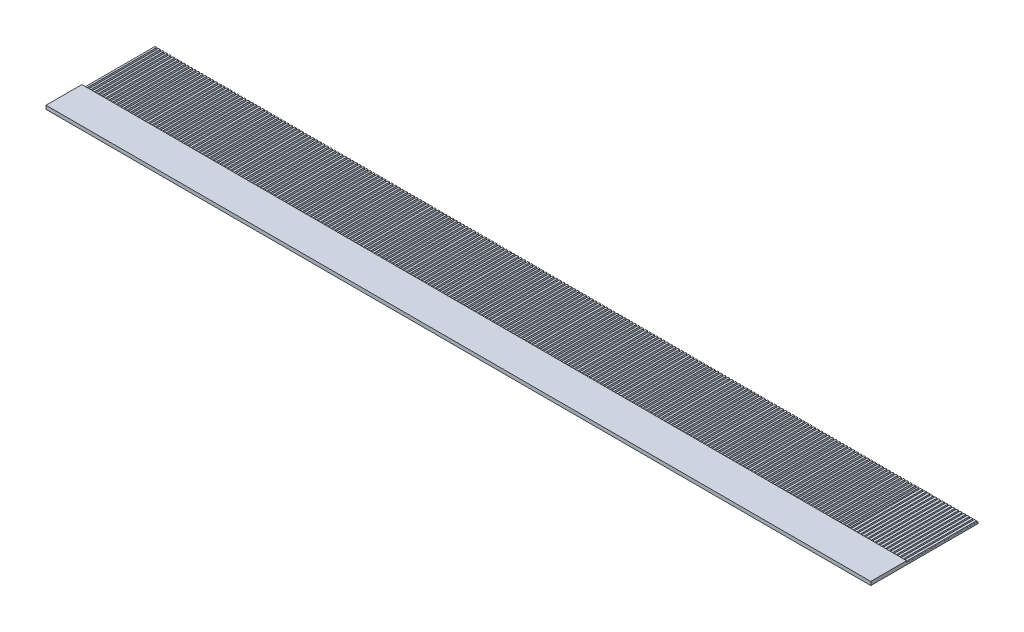
SolidWorks part; units mm, degrees
ref_plane "Front Plane" through (0, 0, 0) normal (0, 0, 1) x (1, 0, 0)
ref_plane "Top Plane" through (0, 0, 0) normal (0, 1, 0) x (1, 0, 0)
ref_plane "Right Plane" through (0, 0, 0) normal (1, 0, 0) x (0, 0, -1)
sketch "Sketch1" plane through (0, 0, 0) normal (0, 1, 0) x (1, 0, 0)
  line L1 (0, 0) -> (115, 0)
  line L2 (0, 0) -> (0, 15)
  line L3 (0, 15) -> (115, 15)
  line L4 (115, 0) -> (115, 15)
extrude "Boss-Extrude1" add sketch "Sketch1" along normal blind 0.5
sketch "Sketch3" plane through (0, 0.5, 0) normal (0, 1, 0) x (1, 0, 0)
  line L0 (115, 0) -> (115, 15) construction
  line L1 (0, 15) -> (115, 15)
  line L2 (0, 15) -> (0, 5)
  line L3 (0, 5) -> (115, 5)
  line L4 (115, 15) -> (115, 5)
extrude "Cut-Extrude3" cut sketch "Sketch3" against normal blind 0.25
sketch "Sketch5" plane through (0, 0.25, 0) normal (0, 1, 0) x (1, 0, 0)
  line L0 (0, 5) -> (115, 5) construction
  line L1 (0, 15) -> (0.25, 15)
  line L2 (0, 15) -> (0, 5)
  line L3 (0, 5) -> (0.25, 5)
  line L4 (0.25, 15) -> (0.25, 5)
  line L5 (0.4954, 14.999) -> (0.7454, 14.999)
  line L6 (0.4954, 14.999) -> (0.4954, 4.999)
  line L7 (0.4954, 4.999) -> (0.7454, 4.999)
  line L8 (0.7454, 14.999) -> (0.7454, 4.999)
  line L9 (0.9914, 15.0028) -> (1.2414, 15.0028)
  line L10 (0.9914, 15.0028) -> (0.9914, 5.0028)
  line L11 (0.9914, 5.0028) -> (1.2414, 5.0028)
  line L12 (1.2414, 15.0028) -> (1.2414, 5.0028)
  line L13 (1.4959, 15.002) -> (1.7459, 15.002)
  line L14 (1.4959, 15.002) -> (1.4959, 5.002)
  line L15 (1.4959, 5.002) -> (1.7459, 5.002)
  line L16 (1.7459, 15.002) -> (1.7459, 5.002)
  line L17 (1.9913, 15.0009) -> (2.2413, 15.0009)
  line L18 (1.9913, 15.0009) -> (1.9913, 5.0009)
  line L19 (1.9913, 5.0009) -> (2.2413, 5.0009)
  line L20 (2.2413, 15.0009) -> (2.2413, 5.0009)
  line L21 (2.4872, 15.0047) -> (2.7372, 15.0047)
  line L22 (2.4872, 15.0047) -> (2.4872, 5.0047)
  line L23 (2.4872, 5.0047) -> (2.7372, 5.0047)
  line L24 (2.7372, 15.0047) -> (2.7372, 5.0047)
  line L25 (3.0149, 14.998) -> (3.2649, 14.998)
  line L26 (3.0149, 14.998) -> (3.0149, 4.998)
  line L27 (3.0149, 4.998) -> (3.2649, 4.998)
  line L28 (3.2649, 14.998) -> (3.2649, 4.998)
  line L29 (3.5104, 14.9969) -> (3.7604, 14.9969)
  line L30 (3.5104, 14.9969) -> (3.5104, 4.9969)
  line L31 (3.5104, 4.9969) -> (3.7604, 4.9969)
  line L32 (3.7604, 14.9969) -> (3.7604, 4.9969)
  line L33 (4.0063, 15.0007) -> (4.2563, 15.0007)
  line L34 (4.0063, 15.0007) -> (4.0063, 5.0007)
  line L35 (4.0063, 5.0007) -> (4.2563, 5.0007)
  line L36 (4.2563, 15.0007) -> (4.2563, 5.0007)
  line L37 (4.5108, 14.9999) -> (4.7608, 14.9999)
  line L38 (4.5108, 14.9999) -> (4.5108, 4.9999)
  line L39 (4.5108, 4.9999) -> (4.7608, 4.9999)
  line L40 (4.7608, 14.9999) -> (4.7608, 4.9999)
  line L41 (5.0062, 14.9989) -> (5.2562, 14.9989)
  line L42 (5.0062, 14.9989) -> (5.0062, 4.9989)
  line L43 (5.0062, 4.9989) -> (5.2562, 4.9989)
  line L44 (5.2562, 14.9989) -> (5.2562, 4.9989)
  line L45 (5.5021, 15.0027) -> (5.7521, 15.0027)
  line L46 (5.5021, 15.0027) -> (5.5021, 5.0027)
  line L47 (5.5021, 5.0027) -> (5.7521, 5.0027)
  line L48 (5.7521, 15.0027) -> (5.7521, 5.0027)
  line L49 (5.9811, 14.9963) -> (6.2311, 14.9963)
  line L50 (5.9811, 14.9963) -> (5.9811, 4.9963)
  line L51 (5.9811, 4.9963) -> (6.2311, 4.9963)
  line L52 (6.2311, 14.9963) -> (6.2311, 4.9963)
  line L53 (6.4766, 14.9953) -> (6.7266, 14.9953)
  line L54 (6.4766, 14.9953) -> (6.4766, 4.9953)
  line L55 (6.4766, 4.9953) -> (6.7266, 4.9953)
  line L56 (6.7266, 14.9953) -> (6.7266, 4.9953)
  line L57 (6.9725, 14.9991) -> (7.2225, 14.9991)
  line L58 (6.9725, 14.9991) -> (6.9725, 4.9991)
  line L59 (6.9725, 4.9991) -> (7.2225, 4.9991)
  line L60 (7.2225, 14.9991) -> (7.2225, 4.9991)
  line L61 (7.477, 14.9983) -> (7.727, 14.9983)
  line L62 (7.477, 14.9983) -> (7.477, 4.9983)
  line L63 (7.477, 4.9983) -> (7.727, 4.9983)
  line L64 (7.727, 14.9983) -> (7.727, 4.9983)
  line L65 (7.9724, 14.9973) -> (8.2224, 14.9973)
  line L66 (7.9724, 14.9973) -> (7.9724, 4.9973)
  line L67 (7.9724, 4.9973) -> (8.2224, 4.9973)
  line L68 (8.2224, 14.9973) -> (8.2224, 4.9973)
  line L69 (8.4683, 15.0011) -> (8.7183, 15.0011)
  line L70 (8.4683, 15.0011) -> (8.4683, 5.0011)
  line L71 (8.4683, 5.0011) -> (8.7183, 5.0011)
  line L72 (8.7183, 15.0011) -> (8.7183, 5.0011)
  line L73 (8.996, 14.9943) -> (9.246, 14.9943)
  line L74 (8.996, 14.9943) -> (8.996, 4.9943)
  line L75 (8.996, 4.9943) -> (9.246, 4.9943)
  line L76 (9.246, 14.9943) -> (9.246, 4.9943)
  line L77 (9.4915, 14.9933) -> (9.7415, 14.9933)
  line L78 (9.4915, 14.9933) -> (9.4915, 4.9933)
  line L79 (9.4915, 4.9933) -> (9.7415, 4.9933)
  line L80 (9.7415, 14.9933) -> (9.7415, 4.9933)
  line L81 (9.9874, 14.9971) -> (10.2374, 14.9971)
  line L82 (9.9874, 14.9971) -> (9.9874, 4.9971)
  line L83 (9.9874, 4.9971) -> (10.2374, 4.9971)
  line L84 (10.2374, 14.9971) -> (10.2374, 4.9971)
  line L85 (10.4919, 14.9963) -> (10.7419, 14.9963)
  line L86 (10.4919, 14.9963) -> (10.4919, 4.9963)
  line L87 (10.4919, 4.9963) -> (10.7419, 4.9963)
  line L88 (10.7419, 14.9963) -> (10.7419, 4.9963)
  line L89 (10.9873, 14.9952) -> (11.2373, 14.9952)
  line L90 (10.9873, 14.9952) -> (10.9873, 4.9952)
  line L91 (10.9873, 4.9952) -> (11.2373, 4.9952)
  line L92 (11.2373, 14.9952) -> (11.2373, 4.9952)
  line L93 (11.4833, 14.999) -> (11.7333, 14.999)
  line L94 (11.4833, 14.999) -> (11.4833, 4.999)
  line L95 (11.4833, 4.999) -> (11.7333, 4.999)
  line L96 (11.7333, 14.999) -> (11.7333, 4.999)
  line L97 (11.9724, 15.0297) -> (12.2224, 15.0297)
  line L98 (11.9724, 15.0297) -> (11.9724, 5.0297)
  line L99 (11.9724, 5.0297) -> (12.2224, 5.0297)
  line L100 (12.2224, 15.0297) -> (12.2224, 5.0297)
  line L101 (12.4678, 15.0286) -> (12.7178, 15.0286)
  line L102 (12.4678, 15.0286) -> (12.4678, 5.0286)
  line L103 (12.4678, 5.0286) -> (12.7178, 5.0286)
  line L104 (12.7178, 15.0286) -> (12.7178, 5.0286)
  line L105 (12.9637, 15.0325) -> (13.2137, 15.0325)
  line L106 (12.9637, 15.0325) -> (12.9637, 5.0325)
  line L107 (12.9637, 5.0325) -> (13.2137, 5.0325)
  line L108 (13.2137, 15.0325) -> (13.2137, 5.0325)
  line L109 (13.4683, 15.0316) -> (13.7183, 15.0316)
  line L110 (13.4683, 15.0316) -> (13.4683, 5.0316)
  line L111 (13.4683, 5.0316) -> (13.7183, 5.0316)
  line L112 (13.7183, 15.0316) -> (13.7183, 5.0316)
  line L113 (13.9637, 15.0306) -> (14.2137, 15.0306)
  line L114 (13.9637, 15.0306) -> (13.9637, 5.0306)
  line L115 (13.9637, 5.0306) -> (14.2137, 5.0306)
  line L116 (14.2137, 15.0306) -> (14.2137, 5.0306)
  line L117 (14.4596, 15.0344) -> (14.7096, 15.0344)
  line L118 (14.4596, 15.0344) -> (14.4596, 5.0344)
  line L119 (14.4596, 5.0344) -> (14.7096, 5.0344)
  line L120 (14.7096, 15.0344) -> (14.7096, 5.0344)
  line L121 (14.9873, 15.0276) -> (15.2373, 15.0276)
  line L122 (14.9873, 15.0276) -> (14.9873, 5.0276)
  line L123 (14.9873, 5.0276) -> (15.2373, 5.0276)
  line L124 (15.2373, 15.0276) -> (15.2373, 5.0276)
  line L125 (15.4827, 15.0266) -> (15.7327, 15.0266)
  line L126 (15.4827, 15.0266) -> (15.4827, 5.0266)
  line L127 (15.4827, 5.0266) -> (15.7327, 5.0266)
  line L128 (15.7327, 15.0266) -> (15.7327, 5.0266)
  line L129 (15.9787, 15.0304) -> (16.2287, 15.0304)
  line L130 (15.9787, 15.0304) -> (15.9787, 5.0304)
  line L131 (15.9787, 5.0304) -> (16.2287, 5.0304)
  line L132 (16.2287, 15.0304) -> (16.2287, 5.0304)
  line L133 (16.4832, 15.0296) -> (16.7332, 15.0296)
  line L134 (16.4832, 15.0296) -> (16.4832, 5.0296)
  line L135 (16.4832, 5.0296) -> (16.7332, 5.0296)
  line L136 (16.7332, 15.0296) -> (16.7332, 5.0296)
  line L137 (16.9786, 15.0286) -> (17.2286, 15.0286)
  line L138 (16.9786, 15.0286) -> (16.9786, 5.0286)
  line L139 (16.9786, 5.0286) -> (17.2286, 5.0286)
  line L140 (17.2286, 15.0286) -> (17.2286, 5.0286)
  line L141 (17.4745, 15.0324) -> (17.7245, 15.0324)
  line L142 (17.4745, 15.0324) -> (17.4745, 5.0324)
  line L143 (17.4745, 5.0324) -> (17.7245, 5.0324)
  line L144 (17.7245, 15.0324) -> (17.7245, 5.0324)
  line L145 (17.9535, 15.026) -> (18.2035, 15.026)
  line L146 (17.9535, 15.026) -> (17.9535, 5.026)
  line L147 (17.9535, 5.026) -> (18.2035, 5.026)
  line L148 (18.2035, 15.026) -> (18.2035, 5.026)
  line L149 (18.449, 15.025) -> (18.699, 15.025)
  line L150 (18.449, 15.025) -> (18.449, 5.025)
  line L151 (18.449, 5.025) -> (18.699, 5.025)
  line L152 (18.699, 15.025) -> (18.699, 5.025)
  line L153 (18.9449, 15.0288) -> (19.1949, 15.0288)
  line L154 (18.9449, 15.0288) -> (18.9449, 5.0288)
  line L155 (18.9449, 5.0288) -> (19.1949, 5.0288)
  line L156 (19.1949, 15.0288) -> (19.1949, 5.0288)
  line L157 (19.4494, 15.028) -> (19.6994, 15.028)
  line L158 (19.4494, 15.028) -> (19.4494, 5.028)
  line L159 (19.4494, 5.028) -> (19.6994, 5.028)
  line L160 (19.6994, 15.028) -> (19.6994, 5.028)
  line L161 (19.9448, 15.0269) -> (20.1948, 15.0269)
  line L162 (19.9448, 15.0269) -> (19.9448, 5.0269)
  line L163 (19.9448, 5.0269) -> (20.1948, 5.0269)
  line L164 (20.1948, 15.0269) -> (20.1948, 5.0269)
  line L165 (20.4407, 15.0308) -> (20.6907, 15.0308)
  line L166 (20.4407, 15.0308) -> (20.4407, 5.0308)
  line L167 (20.4407, 5.0308) -> (20.6907, 5.0308)
  line L168 (20.6907, 15.0308) -> (20.6907, 5.0308)
  line L169 (20.9684, 15.024) -> (21.2184, 15.024)
  line L170 (20.9684, 15.024) -> (20.9684, 5.024)
  line L171 (20.9684, 5.024) -> (21.2184, 5.024)
  line L172 (21.2184, 15.024) -> (21.2184, 5.024)
  line L173 (21.4639, 15.0229) -> (21.7139, 15.0229)
  line L174 (21.4639, 15.0229) -> (21.4639, 5.0229)
  line L175 (21.4639, 5.0229) -> (21.7139, 5.0229)
  line L176 (21.7139, 15.0229) -> (21.7139, 5.0229)
  line L177 (21.9598, 15.0268) -> (22.2098, 15.0268)
  line L178 (21.9598, 15.0268) -> (21.9598, 5.0268)
  line L179 (21.9598, 5.0268) -> (22.2098, 5.0268)
  line L180 (22.2098, 15.0268) -> (22.2098, 5.0268)
  line L181 (22.4643, 15.0259) -> (22.7143, 15.0259)
  line L182 (22.4643, 15.0259) -> (22.4643, 5.0259)
  line L183 (22.4643, 5.0259) -> (22.7143, 5.0259)
  line L184 (22.7143, 15.0259) -> (22.7143, 5.0259)
  line L185 (22.9597, 15.0249) -> (23.2097, 15.0249)
  line L186 (22.9597, 15.0249) -> (22.9597, 5.0249)
  line L187 (22.9597, 5.0249) -> (23.2097, 5.0249)
  line L188 (23.2097, 15.0249) -> (23.2097, 5.0249)
  line L189 (23.4556, 15.0287) -> (23.7056, 15.0287)
  line L190 (23.4556, 15.0287) -> (23.4556, 5.0287)
  line L191 (23.4556, 5.0287) -> (23.7056, 5.0287)
  line L192 (23.7056, 15.0287) -> (23.7056, 5.0287)
  line L193 (23.9759, 15.0248) -> (24.2259, 15.0248)
  line L194 (23.9759, 15.0248) -> (23.9759, 5.0248)
  line L195 (23.9759, 5.0248) -> (24.2259, 5.0248)
  line L196 (24.2259, 15.0248) -> (24.2259, 5.0248)
  line L197 (24.4713, 15.0237) -> (24.7213, 15.0237)
  line L198 (24.4713, 15.0237) -> (24.4713, 5.0237)
  line L199 (24.4713, 5.0237) -> (24.7213, 5.0237)
  line L200 (24.7213, 15.0237) -> (24.7213, 5.0237)
  line L201 (24.9672, 15.0275) -> (25.2172, 15.0275)
  line L202 (24.9672, 15.0275) -> (24.9672, 5.0275)
  line L203 (24.9672, 5.0275) -> (25.2172, 5.0275)
  line L204 (25.2172, 15.0275) -> (25.2172, 5.0275)
  line L205 (25.4717, 15.0267) -> (25.7217, 15.0267)
  line L206 (25.4717, 15.0267) -> (25.4717, 5.0267)
  line L207 (25.4717, 5.0267) -> (25.7217, 5.0267)
  line L208 (25.7217, 15.0267) -> (25.7217, 5.0267)
  line L209 (25.9672, 15.0257) -> (26.2172, 15.0257)
  line L210 (25.9672, 15.0257) -> (25.9672, 5.0257)
  line L211 (25.9672, 5.0257) -> (26.2172, 5.0257)
  line L212 (26.2172, 15.0257) -> (26.2172, 5.0257)
  line L213 (26.4631, 15.0295) -> (26.7131, 15.0295)
  line L214 (26.4631, 15.0295) -> (26.4631, 5.0295)
  line L215 (26.4631, 5.0295) -> (26.7131, 5.0295)
  line L216 (26.7131, 15.0295) -> (26.7131, 5.0295)
  line L217 (26.9908, 15.0227) -> (27.2408, 15.0227)
  line L218 (26.9908, 15.0227) -> (26.9908, 5.0227)
  line L219 (26.9908, 5.0227) -> (27.2408, 5.0227)
  line L220 (27.2408, 15.0227) -> (27.2408, 5.0227)
  line L221 (27.4862, 15.0217) -> (27.7362, 15.0217)
  line L222 (27.4862, 15.0217) -> (27.4862, 5.0217)
  line L223 (27.4862, 5.0217) -> (27.7362, 5.0217)
  line L224 (27.7362, 15.0217) -> (27.7362, 5.0217)
  line L225 (27.9821, 15.0255) -> (28.2321, 15.0255)
  line L226 (27.9821, 15.0255) -> (27.9821, 5.0255)
  line L227 (27.9821, 5.0255) -> (28.2321, 5.0255)
  line L228 (28.2321, 15.0255) -> (28.2321, 5.0255)
  line L229 (28.4866, 15.0247) -> (28.7366, 15.0247)
  line L230 (28.4866, 15.0247) -> (28.4866, 5.0247)
  line L231 (28.4866, 5.0247) -> (28.7366, 5.0247)
  line L232 (28.7366, 15.0247) -> (28.7366, 5.0247)
  line L233 (28.9821, 15.0236) -> (29.2321, 15.0236)
  line L234 (28.9821, 15.0236) -> (28.9821, 5.0236)
  line L235 (28.9821, 5.0236) -> (29.2321, 5.0236)
  line L236 (29.2321, 15.0236) -> (29.2321, 5.0236)
  line L237 (29.478, 15.0275) -> (29.728, 15.0275)
  line L238 (29.478, 15.0275) -> (29.478, 5.0275)
  line L239 (29.478, 5.0275) -> (29.728, 5.0275)
  line L240 (29.728, 15.0275) -> (29.728, 5.0275)
  line L241 (29.957, 15.0211) -> (30.207, 15.0211)
  line L242 (29.957, 15.0211) -> (29.957, 5.0211)
  line L243 (29.957, 5.0211) -> (30.207, 5.0211)
  line L244 (30.207, 15.0211) -> (30.207, 5.0211)
  line L245 (30.4524, 15.0201) -> (30.7024, 15.0201)
  line L246 (30.4524, 15.0201) -> (30.4524, 5.0201)
  line L247 (30.4524, 5.0201) -> (30.7024, 5.0201)
  line L248 (30.7024, 15.0201) -> (30.7024, 5.0201)
  line L249 (30.9483, 15.0239) -> (31.1983, 15.0239)
  line L250 (30.9483, 15.0239) -> (30.9483, 5.0239)
  line L251 (30.9483, 5.0239) -> (31.1983, 5.0239)
  line L252 (31.1983, 15.0239) -> (31.1983, 5.0239)
  line L253 (31.4528, 15.0231) -> (31.7028, 15.0231)
  line L254 (31.4528, 15.0231) -> (31.4528, 5.0231)
  line L255 (31.4528, 5.0231) -> (31.7028, 5.0231)
  line L256 (31.7028, 15.0231) -> (31.7028, 5.0231)
  line L257 (31.9483, 15.022) -> (32.1983, 15.022)
  line L258 (31.9483, 15.022) -> (31.9483, 5.022)
  line L259 (31.9483, 5.022) -> (32.1983, 5.022)
  line L260 (32.1983, 15.022) -> (32.1983, 5.022)
  line L261 (32.4442, 15.0258) -> (32.6942, 15.0258)
  line L262 (32.4442, 15.0258) -> (32.4442, 5.0258)
  line L263 (32.4442, 5.0258) -> (32.6942, 5.0258)
  line L264 (32.6942, 15.0258) -> (32.6942, 5.0258)
  line L265 (32.9719, 15.0191) -> (33.2219, 15.0191)
  line L266 (32.9719, 15.0191) -> (32.9719, 5.0191)
  line L267 (32.9719, 5.0191) -> (33.2219, 5.0191)
  line L268 (33.2219, 15.0191) -> (33.2219, 5.0191)
  line L269 (33.4673, 15.018) -> (33.7173, 15.018)
  line L270 (33.4673, 15.018) -> (33.4673, 5.018)
  line L271 (33.4673, 5.018) -> (33.7173, 5.018)
  line L272 (33.7173, 15.018) -> (33.7173, 5.018)
  line L273 (33.9632, 15.0218) -> (34.2132, 15.0218)
  line L274 (33.9632, 15.0218) -> (33.9632, 5.0218)
  line L275 (33.9632, 5.0218) -> (34.2132, 5.0218)
  line L276 (34.2132, 15.0218) -> (34.2132, 5.0218)
  line L277 (34.4678, 15.021) -> (34.7178, 15.021)
  line L278 (34.4678, 15.021) -> (34.4678, 5.021)
  line L279 (34.4678, 5.021) -> (34.7178, 5.021)
  line L280 (34.7178, 15.021) -> (34.7178, 5.021)
  line L281 (34.9632, 15.02) -> (35.2132, 15.02)
  line L282 (34.9632, 15.02) -> (34.9632, 5.02)
  line L283 (34.9632, 5.02) -> (35.2132, 5.02)
  line L284 (35.2132, 15.02) -> (35.2132, 5.02)
  line L285 (35.4591, 15.0238) -> (35.7091, 15.0238)
  line L286 (35.4591, 15.0238) -> (35.4591, 5.0238)
  line L287 (35.4591, 5.0238) -> (35.7091, 5.0238)
  line L288 (35.7091, 15.0238) -> (35.7091, 5.0238)
  line L289 (35.9482, 15.0544) -> (36.1982, 15.0544)
  line L290 (35.9482, 15.0544) -> (35.9482, 5.0544)
  line L291 (35.9482, 5.0544) -> (36.1982, 5.0544)
  line L292 (36.1982, 15.0544) -> (36.1982, 5.0544)
  line L293 (36.4437, 15.0534) -> (36.6937, 15.0534)
  line L294 (36.4437, 15.0534) -> (36.4437, 5.0534)
  line L295 (36.4437, 5.0534) -> (36.6937, 5.0534)
  line L296 (36.6937, 15.0534) -> (36.6937, 5.0534)
  line L297 (36.9396, 15.0572) -> (37.1896, 15.0572)
  line L298 (36.9396, 15.0572) -> (36.9396, 5.0572)
  line L299 (36.9396, 5.0572) -> (37.1896, 5.0572)
  line L300 (37.1896, 15.0572) -> (37.1896, 5.0572)
  line L301 (37.4441, 15.0564) -> (37.6941, 15.0564)
  line L302 (37.4441, 15.0564) -> (37.4441, 5.0564)
  line L303 (37.4441, 5.0564) -> (37.6941, 5.0564)
  line L304 (37.6941, 15.0564) -> (37.6941, 5.0564)
  line L305 (37.9396, 15.0554) -> (38.1896, 15.0554)
  line L306 (37.9396, 15.0554) -> (37.9396, 5.0554)
  line L307 (37.9396, 5.0554) -> (38.1896, 5.0554)
  line L308 (38.1896, 15.0554) -> (38.1896, 5.0554)
  line L309 (38.4355, 15.0592) -> (38.6855, 15.0592)
  line L310 (38.4355, 15.0592) -> (38.4355, 5.0592)
  line L311 (38.4355, 5.0592) -> (38.6855, 5.0592)
  line L312 (38.6855, 15.0592) -> (38.6855, 5.0592)
  line L313 (38.9632, 15.0524) -> (39.2132, 15.0524)
  line L314 (38.9632, 15.0524) -> (38.9632, 5.0524)
  line L315 (38.9632, 5.0524) -> (39.2132, 5.0524)
  line L316 (39.2132, 15.0524) -> (39.2132, 5.0524)
  line L317 (39.4586, 15.0514) -> (39.7086, 15.0514)
  line L318 (39.4586, 15.0514) -> (39.4586, 5.0514)
  line L319 (39.4586, 5.0514) -> (39.7086, 5.0514)
  line L320 (39.7086, 15.0514) -> (39.7086, 5.0514)
  line L321 (39.9545, 15.0552) -> (40.2045, 15.0552)
  line L322 (39.9545, 15.0552) -> (39.9545, 5.0552)
  line L323 (39.9545, 5.0552) -> (40.2045, 5.0552)
  line L324 (40.2045, 15.0552) -> (40.2045, 5.0552)
  line L325 (40.459, 15.0544) -> (40.709, 15.0544)
  line L326 (40.459, 15.0544) -> (40.459, 5.0544)
  line L327 (40.459, 5.0544) -> (40.709, 5.0544)
  line L328 (40.709, 15.0544) -> (40.709, 5.0544)
  line L329 (40.9545, 15.0533) -> (41.2045, 15.0533)
  line L330 (40.9545, 15.0533) -> (40.9545, 5.0533)
  line L331 (40.9545, 5.0533) -> (41.2045, 5.0533)
  line L332 (41.2045, 15.0533) -> (41.2045, 5.0533)
  line L333 (41.4504, 15.0571) -> (41.7004, 15.0571)
  line L334 (41.4504, 15.0571) -> (41.4504, 5.0571)
  line L335 (41.4504, 5.0571) -> (41.7004, 5.0571)
  line L336 (41.7004, 15.0571) -> (41.7004, 5.0571)
  line L337 (41.9294, 15.0508) -> (42.1794, 15.0508)
  line L338 (41.9294, 15.0508) -> (41.9294, 5.0508)
  line L339 (41.9294, 5.0508) -> (42.1794, 5.0508)
  line L340 (42.1794, 15.0508) -> (42.1794, 5.0508)
  line L341 (42.4248, 15.0497) -> (42.6748, 15.0497)
  line L342 (42.4248, 15.0497) -> (42.4248, 5.0497)
  line L343 (42.4248, 5.0497) -> (42.6748, 5.0497)
  line L344 (42.6748, 15.0497) -> (42.6748, 5.0497)
  line L345 (42.9207, 15.0536) -> (43.1707, 15.0536)
  line L346 (42.9207, 15.0536) -> (42.9207, 5.0536)
  line L347 (42.9207, 5.0536) -> (43.1707, 5.0536)
  line L348 (43.1707, 15.0536) -> (43.1707, 5.0536)
  line L349 (43.4252, 15.0527) -> (43.6752, 15.0527)
  line L350 (43.4252, 15.0527) -> (43.4252, 5.0527)
  line L351 (43.4252, 5.0527) -> (43.6752, 5.0527)
  line L352 (43.6752, 15.0527) -> (43.6752, 5.0527)
  line L353 (43.9207, 15.0517) -> (44.1707, 15.0517)
  line L354 (43.9207, 15.0517) -> (43.9207, 5.0517)
  line L355 (43.9207, 5.0517) -> (44.1707, 5.0517)
  line L356 (44.1707, 15.0517) -> (44.1707, 5.0517)
  line L357 (44.4166, 15.0555) -> (44.6666, 15.0555)
  line L358 (44.4166, 15.0555) -> (44.4166, 5.0555)
  line L359 (44.4166, 5.0555) -> (44.6666, 5.0555)
  line L360 (44.6666, 15.0555) -> (44.6666, 5.0555)
  line L361 (44.9443, 15.0487) -> (45.1943, 15.0487)
  line L362 (44.9443, 15.0487) -> (44.9443, 5.0487)
  line L363 (44.9443, 5.0487) -> (45.1943, 5.0487)
  line L364 (45.1943, 15.0487) -> (45.1943, 5.0487)
  line L365 (45.4397, 15.0477) -> (45.6897, 15.0477)
  line L366 (45.4397, 15.0477) -> (45.4397, 5.0477)
  line L367 (45.4397, 5.0477) -> (45.6897, 5.0477)
  line L368 (45.6897, 15.0477) -> (45.6897, 5.0477)
  line L369 (45.9356, 15.0515) -> (46.1856, 15.0515)
  line L370 (45.9356, 15.0515) -> (45.9356, 5.0515)
  line L371 (45.9356, 5.0515) -> (46.1856, 5.0515)
  line L372 (46.1856, 15.0515) -> (46.1856, 5.0515)
  line L373 (46.4401, 15.0507) -> (46.6901, 15.0507)
  line L374 (46.4401, 15.0507) -> (46.4401, 5.0507)
  line L375 (46.4401, 5.0507) -> (46.6901, 5.0507)
  line L376 (46.6901, 15.0507) -> (46.6901, 5.0507)
  line L377 (46.9356, 15.0497) -> (47.1856, 15.0497)
  line L378 (46.9356, 15.0497) -> (46.9356, 5.0497)
  line L379 (46.9356, 5.0497) -> (47.1856, 5.0497)
  line L380 (47.1856, 15.0497) -> (47.1856, 5.0497)
  line L381 (47.4315, 15.0535) -> (47.6815, 15.0535)
  line L382 (47.4315, 15.0535) -> (47.4315, 5.0535)
  line L383 (47.4315, 5.0535) -> (47.6815, 5.0535)
  line L384 (47.6815, 15.0535) -> (47.6815, 5.0535)
  line L385 (47.9359, 14.9579) -> (48.1859, 14.9579)
  line L386 (47.9359, 14.9579) -> (47.9359, 4.9579)
  line L387 (47.9359, 4.9579) -> (48.1859, 4.9579)
  line L388 (48.1859, 14.9579) -> (48.1859, 4.9579)
  line L389 (48.4313, 14.9568) -> (48.6813, 14.9568)
  line L390 (48.4313, 14.9568) -> (48.4313, 4.9568)
  line L391 (48.4313, 4.9568) -> (48.6813, 4.9568)
  line L392 (48.6813, 14.9568) -> (48.6813, 4.9568)
  line L393 (48.9273, 14.9606) -> (49.1773, 14.9606)
  line L394 (48.9273, 14.9606) -> (48.9273, 4.9606)
  line L395 (48.9273, 4.9606) -> (49.1773, 4.9606)
  line L396 (49.1773, 14.9606) -> (49.1773, 4.9606)
  line L397 (49.4318, 14.9598) -> (49.6818, 14.9598)
  line L398 (49.4318, 14.9598) -> (49.4318, 4.9598)
  line L399 (49.4318, 4.9598) -> (49.6818, 4.9598)
  line L400 (49.6818, 14.9598) -> (49.6818, 4.9598)
  line L401 (49.9272, 14.9588) -> (50.1772, 14.9588)
  line L402 (49.9272, 14.9588) -> (49.9272, 4.9588)
  line L403 (49.9272, 4.9588) -> (50.1772, 4.9588)
  line L404 (50.1772, 14.9588) -> (50.1772, 4.9588)
  line L405 (50.4231, 14.9626) -> (50.6731, 14.9626)
  line L406 (50.4231, 14.9626) -> (50.4231, 4.9626)
  line L407 (50.4231, 4.9626) -> (50.6731, 4.9626)
  line L408 (50.6731, 14.9626) -> (50.6731, 4.9626)
  line L409 (50.9508, 14.9558) -> (51.2008, 14.9558)
  line L410 (50.9508, 14.9558) -> (50.9508, 4.9558)
  line L411 (50.9508, 4.9558) -> (51.2008, 4.9558)
  line L412 (51.2008, 14.9558) -> (51.2008, 4.9558)
  line L413 (51.4463, 14.9548) -> (51.6963, 14.9548)
  line L414 (51.4463, 14.9548) -> (51.4463, 4.9548)
  line L415 (51.4463, 4.9548) -> (51.6963, 4.9548)
  line L416 (51.6963, 14.9548) -> (51.6963, 4.9548)
  line L417 (51.9422, 14.9586) -> (52.1922, 14.9586)
  line L418 (51.9422, 14.9586) -> (51.9422, 4.9586)
  line L419 (51.9422, 4.9586) -> (52.1922, 4.9586)
  line L420 (52.1922, 14.9586) -> (52.1922, 4.9586)
  line L421 (52.4467, 14.9578) -> (52.6967, 14.9578)
  line L422 (52.4467, 14.9578) -> (52.4467, 4.9578)
  line L423 (52.4467, 4.9578) -> (52.6967, 4.9578)
  line L424 (52.6967, 14.9578) -> (52.6967, 4.9578)
  line L425 (52.9421, 14.9567) -> (53.1921, 14.9567)
  line L426 (52.9421, 14.9567) -> (52.9421, 4.9567)
  line L427 (52.9421, 4.9567) -> (53.1921, 4.9567)
  line L428 (53.1921, 14.9567) -> (53.1921, 4.9567)
  line L429 (53.438, 14.9606) -> (53.688, 14.9606)
  line L430 (53.438, 14.9606) -> (53.438, 4.9606)
  line L431 (53.438, 4.9606) -> (53.688, 4.9606)
  line L432 (53.688, 14.9606) -> (53.688, 4.9606)
  line L433 (53.917, 14.9542) -> (54.167, 14.9542)
  line L434 (53.917, 14.9542) -> (53.917, 4.9542)
  line L435 (53.917, 4.9542) -> (54.167, 4.9542)
  line L436 (54.167, 14.9542) -> (54.167, 4.9542)
  line L437 (54.4125, 14.9532) -> (54.6625, 14.9532)
  line L438 (54.4125, 14.9532) -> (54.4125, 4.9532)
  line L439 (54.4125, 4.9532) -> (54.6625, 4.9532)
  line L440 (54.6625, 14.9532) -> (54.6625, 4.9532)
  line L441 (54.9084, 14.957) -> (55.1584, 14.957)
  line L442 (54.9084, 14.957) -> (54.9084, 4.957)
  line L443 (54.9084, 4.957) -> (55.1584, 4.957)
  line L444 (55.1584, 14.957) -> (55.1584, 4.957)
  line L445 (55.4129, 14.9562) -> (55.6629, 14.9562)
  line L446 (55.4129, 14.9562) -> (55.4129, 4.9562)
  line L447 (55.4129, 4.9562) -> (55.6629, 4.9562)
  line L448 (55.6629, 14.9562) -> (55.6629, 4.9562)
  line L449 (55.9083, 14.9551) -> (56.1583, 14.9551)
  line L450 (55.9083, 14.9551) -> (55.9083, 4.9551)
  line L451 (55.9083, 4.9551) -> (56.1583, 4.9551)
  line L452 (56.1583, 14.9551) -> (56.1583, 4.9551)
  line L453 (56.4042, 14.9589) -> (56.6542, 14.9589)
  line L454 (56.4042, 14.9589) -> (56.4042, 4.9589)
  line L455 (56.4042, 4.9589) -> (56.6542, 4.9589)
  line L456 (56.6542, 14.9589) -> (56.6542, 4.9589)
  line L457 (56.9319, 14.9522) -> (57.1819, 14.9522)
  line L458 (56.9319, 14.9522) -> (56.9319, 4.9522)
  line L459 (56.9319, 4.9522) -> (57.1819, 4.9522)
  line L460 (57.1819, 14.9522) -> (57.1819, 4.9522)
  line L461 (57.4274, 14.9511) -> (57.6774, 14.9511)
  line L462 (57.4274, 14.9511) -> (57.4274, 4.9511)
  line L463 (57.4274, 4.9511) -> (57.6774, 4.9511)
  line L464 (57.6774, 14.9511) -> (57.6774, 4.9511)
  line L465 (57.9233, 14.9549) -> (58.1733, 14.9549)
  line L466 (57.9233, 14.9549) -> (57.9233, 4.9549)
  line L467 (57.9233, 4.9549) -> (58.1733, 4.9549)
  line L468 (58.1733, 14.9549) -> (58.1733, 4.9549)
  line L469 (58.4278, 14.9541) -> (58.6778, 14.9541)
  line L470 (58.4278, 14.9541) -> (58.4278, 4.9541)
  line L471 (58.4278, 4.9541) -> (58.6778, 4.9541)
  line L472 (58.6778, 14.9541) -> (58.6778, 4.9541)
  line L473 (58.9233, 14.9531) -> (59.1733, 14.9531)
  line L474 (58.9233, 14.9531) -> (58.9233, 4.9531)
  line L475 (58.9233, 4.9531) -> (59.1733, 4.9531)
  line L476 (59.1733, 14.9531) -> (59.1733, 4.9531)
  line L477 (59.4192, 14.9569) -> (59.6692, 14.9569)
  line L478 (59.4192, 14.9569) -> (59.4192, 4.9569)
  line L479 (59.4192, 4.9569) -> (59.6692, 4.9569)
  line L480 (59.6692, 14.9569) -> (59.6692, 4.9569)
  line L481 (59.9083, 14.9875) -> (60.1583, 14.9875)
  line L482 (59.9083, 14.9875) -> (59.9083, 4.9875)
  line L483 (59.9083, 4.9875) -> (60.1583, 4.9875)
  line L484 (60.1583, 14.9875) -> (60.1583, 4.9875)
  line L485 (60.4037, 14.9865) -> (60.6537, 14.9865)
  line L486 (60.4037, 14.9865) -> (60.4037, 4.9865)
  line L487 (60.4037, 4.9865) -> (60.6537, 4.9865)
  line L488 (60.6537, 14.9865) -> (60.6537, 4.9865)
  line L489 (60.8996, 14.9903) -> (61.1496, 14.9903)
  line L490 (60.8996, 14.9903) -> (60.8996, 4.9903)
  line L491 (60.8996, 4.9903) -> (61.1496, 4.9903)
  line L492 (61.1496, 14.9903) -> (61.1496, 4.9903)
  line L493 (61.4042, 14.9895) -> (61.6542, 14.9895)
  line L494 (61.4042, 14.9895) -> (61.4042, 4.9895)
  line L495 (61.4042, 4.9895) -> (61.6542, 4.9895)
  line L496 (61.6542, 14.9895) -> (61.6542, 4.9895)
  line L497 (61.8996, 14.9885) -> (62.1496, 14.9885)
  line L498 (61.8996, 14.9885) -> (61.8996, 4.9885)
  line L499 (61.8996, 4.9885) -> (62.1496, 4.9885)
  line L500 (62.1496, 14.9885) -> (62.1496, 4.9885)
  line L501 (62.3955, 14.9923) -> (62.6455, 14.9923)
  line L502 (62.3955, 14.9923) -> (62.3955, 4.9923)
  line L503 (62.3955, 4.9923) -> (62.6455, 4.9923)
  line L504 (62.6455, 14.9923) -> (62.6455, 4.9923)
  line L505 (62.9232, 14.9855) -> (63.1732, 14.9855)
  line L506 (62.9232, 14.9855) -> (62.9232, 4.9855)
  line L507 (62.9232, 4.9855) -> (63.1732, 4.9855)
  line L508 (63.1732, 14.9855) -> (63.1732, 4.9855)
  line L509 (63.4187, 14.9845) -> (63.6687, 14.9845)
  line L510 (63.4187, 14.9845) -> (63.4187, 4.9845)
  line L511 (63.4187, 4.9845) -> (63.6687, 4.9845)
  line L512 (63.6687, 14.9845) -> (63.6687, 4.9845)
  line L513 (63.9146, 14.9883) -> (64.1646, 14.9883)
  line L514 (63.9146, 14.9883) -> (63.9146, 4.9883)
  line L515 (63.9146, 4.9883) -> (64.1646, 4.9883)
  line L516 (64.1646, 14.9883) -> (64.1646, 4.9883)
  line L517 (64.4191, 14.9875) -> (64.6691, 14.9875)
  line L518 (64.4191, 14.9875) -> (64.4191, 4.9875)
  line L519 (64.4191, 4.9875) -> (64.6691, 4.9875)
  line L520 (64.6691, 14.9875) -> (64.6691, 4.9875)
  line L521 (64.9145, 14.9864) -> (65.1645, 14.9864)
  line L522 (64.9145, 14.9864) -> (64.9145, 4.9864)
  line L523 (64.9145, 4.9864) -> (65.1645, 4.9864)
  line L524 (65.1645, 14.9864) -> (65.1645, 4.9864)
  line L525 (65.4104, 14.9902) -> (65.6604, 14.9902)
  line L526 (65.4104, 14.9902) -> (65.4104, 4.9902)
  line L527 (65.4104, 4.9902) -> (65.6604, 4.9902)
  line L528 (65.6604, 14.9902) -> (65.6604, 4.9902)
  line L529 (65.8894, 14.9839) -> (66.1394, 14.9839)
  line L530 (65.8894, 14.9839) -> (65.8894, 4.9839)
  line L531 (65.8894, 4.9839) -> (66.1394, 4.9839)
  line L532 (66.1394, 14.9839) -> (66.1394, 4.9839)
  line L533 (66.3849, 14.9828) -> (66.6349, 14.9828)
  line L534 (66.3849, 14.9828) -> (66.3849, 4.9828)
  line L535 (66.3849, 4.9828) -> (66.6349, 4.9828)
  line L536 (66.6349, 14.9828) -> (66.6349, 4.9828)
  line L537 (66.8808, 14.9867) -> (67.1308, 14.9867)
  line L538 (66.8808, 14.9867) -> (66.8808, 4.9867)
  line L539 (66.8808, 4.9867) -> (67.1308, 4.9867)
  line L540 (67.1308, 14.9867) -> (67.1308, 4.9867)
  line L541 (67.3853, 14.9858) -> (67.6353, 14.9858)
  line L542 (67.3853, 14.9858) -> (67.3853, 4.9858)
  line L543 (67.3853, 4.9858) -> (67.6353, 4.9858)
  line L544 (67.6353, 14.9858) -> (67.6353, 4.9858)
  line L545 (67.8807, 14.9848) -> (68.1307, 14.9848)
  line L546 (67.8807, 14.9848) -> (67.8807, 4.9848)
  line L547 (67.8807, 4.9848) -> (68.1307, 4.9848)
  line L548 (68.1307, 14.9848) -> (68.1307, 4.9848)
  line L549 (68.3766, 14.9886) -> (68.6266, 14.9886)
  line L550 (68.3766, 14.9886) -> (68.3766, 4.9886)
  line L551 (68.3766, 4.9886) -> (68.6266, 4.9886)
  line L552 (68.6266, 14.9886) -> (68.6266, 4.9886)
  line L553 (68.9043, 14.9818) -> (69.1543, 14.9818)
  line L554 (68.9043, 14.9818) -> (68.9043, 4.9818)
  line L555 (68.9043, 4.9818) -> (69.1543, 4.9818)
  line L556 (69.1543, 14.9818) -> (69.1543, 4.9818)
  line L557 (69.3998, 14.9808) -> (69.6498, 14.9808)
  line L558 (69.3998, 14.9808) -> (69.3998, 4.9808)
  line L559 (69.3998, 4.9808) -> (69.6498, 4.9808)
  line L560 (69.6498, 14.9808) -> (69.6498, 4.9808)
  line L561 (69.8957, 14.9846) -> (70.1457, 14.9846)
  line L562 (69.8957, 14.9846) -> (69.8957, 4.9846)
  line L563 (69.8957, 4.9846) -> (70.1457, 4.9846)
  line L564 (70.1457, 14.9846) -> (70.1457, 4.9846)
  line L565 (70.4002, 14.9838) -> (70.6502, 14.9838)
  line L566 (70.4002, 14.9838) -> (70.4002, 4.9838)
  line L567 (70.4002, 4.9838) -> (70.6502, 4.9838)
  line L568 (70.6502, 14.9838) -> (70.6502, 4.9838)
  line L569 (70.8956, 14.9828) -> (71.1456, 14.9828)
  line L570 (70.8956, 14.9828) -> (70.8956, 4.9828)
  line L571 (70.8956, 4.9828) -> (71.1456, 4.9828)
  line L572 (71.1456, 14.9828) -> (71.1456, 4.9828)
  line L573 (71.3916, 14.9866) -> (71.6416, 14.9866)
  line L574 (71.3916, 14.9866) -> (71.3916, 4.9866)
  line L575 (71.3916, 4.9866) -> (71.6416, 4.9866)
  line L576 (71.6416, 14.9866) -> (71.6416, 4.9866)
  line L577 (71.9118, 14.9826) -> (72.1618, 14.9826)
  line L578 (71.9118, 14.9826) -> (71.9118, 4.9826)
  line L579 (71.9118, 4.9826) -> (72.1618, 4.9826)
  line L580 (72.1618, 14.9826) -> (72.1618, 4.9826)
  line L581 (72.4072, 14.9816) -> (72.6572, 14.9816)
  line L582 (72.4072, 14.9816) -> (72.4072, 4.9816)
  line L583 (72.4072, 4.9816) -> (72.6572, 4.9816)
  line L584 (72.6572, 14.9816) -> (72.6572, 4.9816)
  line L585 (72.9031, 14.9854) -> (73.1531, 14.9854)
  line L586 (72.9031, 14.9854) -> (72.9031, 4.9854)
  line L587 (72.9031, 4.9854) -> (73.1531, 4.9854)
  line L588 (73.1531, 14.9854) -> (73.1531, 4.9854)
  line L589 (73.4076, 14.9846) -> (73.6576, 14.9846)
  line L590 (73.4076, 14.9846) -> (73.4076, 4.9846)
  line L591 (73.4076, 4.9846) -> (73.6576, 4.9846)
  line L592 (73.6576, 14.9846) -> (73.6576, 4.9846)
  line L593 (73.9031, 14.9835) -> (74.1531, 14.9835)
  line L594 (73.9031, 14.9835) -> (73.9031, 4.9835)
  line L595 (73.9031, 4.9835) -> (74.1531, 4.9835)
  line L596 (74.1531, 14.9835) -> (74.1531, 4.9835)
  line L597 (74.399, 14.9874) -> (74.649, 14.9874)
  line L598 (74.399, 14.9874) -> (74.399, 4.9874)
  line L599 (74.399, 4.9874) -> (74.649, 4.9874)
  line L600 (74.649, 14.9874) -> (74.649, 4.9874)
  line L601 (74.9267, 14.9806) -> (75.1767, 14.9806)
  line L602 (74.9267, 14.9806) -> (74.9267, 4.9806)
  line L603 (74.9267, 4.9806) -> (75.1767, 4.9806)
  line L604 (75.1767, 14.9806) -> (75.1767, 4.9806)
  line L605 (75.4221, 14.9795) -> (75.6721, 14.9795)
  line L606 (75.4221, 14.9795) -> (75.4221, 4.9795)
  line L607 (75.4221, 4.9795) -> (75.6721, 4.9795)
  line L608 (75.6721, 14.9795) -> (75.6721, 4.9795)
  line L609 (75.918, 14.9834) -> (76.168, 14.9834)
  line L610 (75.918, 14.9834) -> (75.918, 4.9834)
  line L611 (75.918, 4.9834) -> (76.168, 4.9834)
  line L612 (76.168, 14.9834) -> (76.168, 4.9834)
  line L613 (76.4225, 14.9825) -> (76.6725, 14.9825)
  line L614 (76.4225, 14.9825) -> (76.4225, 4.9825)
  line L615 (76.4225, 4.9825) -> (76.6725, 4.9825)
  line L616 (76.6725, 14.9825) -> (76.6725, 4.9825)
  line L617 (76.918, 14.9815) -> (77.168, 14.9815)
  line L618 (76.918, 14.9815) -> (76.918, 4.9815)
  line L619 (76.918, 4.9815) -> (77.168, 4.9815)
  line L620 (77.168, 14.9815) -> (77.168, 4.9815)
  line L621 (77.4139, 14.9853) -> (77.6639, 14.9853)
  line L622 (77.4139, 14.9853) -> (77.4139, 4.9853)
  line L623 (77.4139, 4.9853) -> (77.6639, 4.9853)
  line L624 (77.6639, 14.9853) -> (77.6639, 4.9853)
  line L625 (77.8929, 14.979) -> (78.1429, 14.979)
  line L626 (77.8929, 14.979) -> (77.8929, 4.979)
  line L627 (77.8929, 4.979) -> (78.1429, 4.979)
  line L628 (78.1429, 14.979) -> (78.1429, 4.979)
  line L629 (78.3883, 14.9779) -> (78.6383, 14.9779)
  line L630 (78.3883, 14.9779) -> (78.3883, 4.9779)
  line L631 (78.3883, 4.9779) -> (78.6383, 4.9779)
  line L632 (78.6383, 14.9779) -> (78.6383, 4.9779)
  line L633 (78.8842, 14.9817) -> (79.1342, 14.9817)
  line L634 (78.8842, 14.9817) -> (78.8842, 4.9817)
  line L635 (78.8842, 4.9817) -> (79.1342, 4.9817)
  line L636 (79.1342, 14.9817) -> (79.1342, 4.9817)
  line L637 (79.3887, 14.9809) -> (79.6387, 14.9809)
  line L638 (79.3887, 14.9809) -> (79.3887, 4.9809)
  line L639 (79.3887, 4.9809) -> (79.6387, 4.9809)
  line L640 (79.6387, 14.9809) -> (79.6387, 4.9809)
  line L641 (79.8842, 14.9799) -> (80.1342, 14.9799)
  line L642 (79.8842, 14.9799) -> (79.8842, 4.9799)
  line L643 (79.8842, 4.9799) -> (80.1342, 4.9799)
  line L644 (80.1342, 14.9799) -> (80.1342, 4.9799)
  line L645 (80.3801, 14.9837) -> (80.6301, 14.9837)
  line L646 (80.3801, 14.9837) -> (80.3801, 4.9837)
  line L647 (80.3801, 4.9837) -> (80.6301, 4.9837)
  line L648 (80.6301, 14.9837) -> (80.6301, 4.9837)
  line L649 (80.9078, 14.9769) -> (81.1578, 14.9769)
  line L650 (80.9078, 14.9769) -> (80.9078, 4.9769)
  line L651 (80.9078, 4.9769) -> (81.1578, 4.9769)
  line L652 (81.1578, 14.9769) -> (81.1578, 4.9769)
  line L653 (81.4032, 14.9759) -> (81.6532, 14.9759)
  line L654 (81.4032, 14.9759) -> (81.4032, 4.9759)
  line L655 (81.4032, 4.9759) -> (81.6532, 4.9759)
  line L656 (81.6532, 14.9759) -> (81.6532, 4.9759)
  line L657 (81.8991, 14.9797) -> (82.1491, 14.9797)
  line L658 (81.8991, 14.9797) -> (81.8991, 4.9797)
  line L659 (81.8991, 4.9797) -> (82.1491, 4.9797)
  line L660 (82.1491, 14.9797) -> (82.1491, 4.9797)
  line L661 (82.4037, 14.9789) -> (82.6537, 14.9789)
  line L662 (82.4037, 14.9789) -> (82.4037, 4.9789)
  line L663 (82.4037, 4.9789) -> (82.6537, 4.9789)
  line L664 (82.6537, 14.9789) -> (82.6537, 4.9789)
  line L665 (82.8991, 14.9778) -> (83.1491, 14.9778)
  line L666 (82.8991, 14.9778) -> (82.8991, 4.9778)
  line L667 (82.8991, 4.9778) -> (83.1491, 4.9778)
  line L668 (83.1491, 14.9778) -> (83.1491, 4.9778)
  line L669 (83.395, 14.9817) -> (83.645, 14.9817)
  line L670 (83.395, 14.9817) -> (83.395, 4.9817)
  line L671 (83.395, 4.9817) -> (83.645, 4.9817)
  line L672 (83.645, 14.9817) -> (83.645, 4.9817)
  line L673 (83.8841, 15.0123) -> (84.1341, 15.0123)
  line L674 (83.8841, 15.0123) -> (83.8841, 5.0123)
  line L675 (83.8841, 5.0123) -> (84.1341, 5.0123)
  line L676 (84.1341, 15.0123) -> (84.1341, 5.0123)
  line L677 (84.3796, 15.0113) -> (84.6296, 15.0113)
  line L678 (84.3796, 15.0113) -> (84.3796, 5.0113)
  line L679 (84.3796, 5.0113) -> (84.6296, 5.0113)
  line L680 (84.6296, 15.0113) -> (84.6296, 5.0113)
  line L681 (84.8755, 15.0151) -> (85.1255, 15.0151)
  line L682 (84.8755, 15.0151) -> (84.8755, 5.0151)
  line L683 (84.8755, 5.0151) -> (85.1255, 5.0151)
  line L684 (85.1255, 15.0151) -> (85.1255, 5.0151)
  line L685 (85.38, 15.0143) -> (85.63, 15.0143)
  line L686 (85.38, 15.0143) -> (85.38, 5.0143)
  line L687 (85.38, 5.0143) -> (85.63, 5.0143)
  line L688 (85.63, 15.0143) -> (85.63, 5.0143)
  line L689 (85.8755, 15.0132) -> (86.1255, 15.0132)
  line L690 (85.8755, 15.0132) -> (85.8755, 5.0132)
  line L691 (85.8755, 5.0132) -> (86.1255, 5.0132)
  line L692 (86.1255, 15.0132) -> (86.1255, 5.0132)
  line L693 (86.3714, 15.017) -> (86.6214, 15.017)
  line L694 (86.3714, 15.017) -> (86.3714, 5.017)
  line L695 (86.3714, 5.017) -> (86.6214, 5.017)
  line L696 (86.6214, 15.017) -> (86.6214, 5.017)
  line L697 (86.8991, 15.0103) -> (87.1491, 15.0103)
  line L698 (86.8991, 15.0103) -> (86.8991, 5.0103)
  line L699 (86.8991, 5.0103) -> (87.1491, 5.0103)
  line L700 (87.1491, 15.0103) -> (87.1491, 5.0103)
  line L701 (87.3945, 15.0092) -> (87.6445, 15.0092)
  line L702 (87.3945, 15.0092) -> (87.3945, 5.0092)
  line L703 (87.3945, 5.0092) -> (87.6445, 5.0092)
  line L704 (87.6445, 15.0092) -> (87.6445, 5.0092)
  line L705 (87.8904, 15.013) -> (88.1404, 15.013)
  line L706 (87.8904, 15.013) -> (87.8904, 5.013)
  line L707 (87.8904, 5.013) -> (88.1404, 5.013)
  line L708 (88.1404, 15.013) -> (88.1404, 5.013)
  line L709 (88.3949, 15.0122) -> (88.6449, 15.0122)
  line L710 (88.3949, 15.0122) -> (88.3949, 5.0122)
  line L711 (88.3949, 5.0122) -> (88.6449, 5.0122)
  line L712 (88.6449, 15.0122) -> (88.6449, 5.0122)
  line L713 (88.8904, 15.0112) -> (89.1404, 15.0112)
  line L714 (88.8904, 15.0112) -> (88.8904, 5.0112)
  line L715 (88.8904, 5.0112) -> (89.1404, 5.0112)
  line L716 (89.1404, 15.0112) -> (89.1404, 5.0112)
  line L717 (89.3863, 15.015) -> (89.6363, 15.015)
  line L718 (89.3863, 15.015) -> (89.3863, 5.015)
  line L719 (89.3863, 5.015) -> (89.6363, 5.015)
  line L720 (89.6363, 15.015) -> (89.6363, 5.015)
  line L721 (89.8653, 15.0086) -> (90.1153, 15.0086)
  line L722 (89.8653, 15.0086) -> (89.8653, 5.0086)
  line L723 (89.8653, 5.0086) -> (90.1153, 5.0086)
  line L724 (90.1153, 15.0086) -> (90.1153, 5.0086)
  line L725 (90.3607, 15.0076) -> (90.6107, 15.0076)
  line L726 (90.3607, 15.0076) -> (90.3607, 5.0076)
  line L727 (90.3607, 5.0076) -> (90.6107, 5.0076)
  line L728 (90.6107, 15.0076) -> (90.6107, 5.0076)
  line L729 (90.8566, 15.0114) -> (91.1066, 15.0114)
  line L730 (90.8566, 15.0114) -> (90.8566, 5.0114)
  line L731 (90.8566, 5.0114) -> (91.1066, 5.0114)
  line L732 (91.1066, 15.0114) -> (91.1066, 5.0114)
  line L733 (91.3611, 15.0106) -> (91.6111, 15.0106)
  line L734 (91.3611, 15.0106) -> (91.3611, 5.0106)
  line L735 (91.3611, 5.0106) -> (91.6111, 5.0106)
  line L736 (91.6111, 15.0106) -> (91.6111, 5.0106)
  line L737 (91.8566, 15.0096) -> (92.1066, 15.0096)
  line L738 (91.8566, 15.0096) -> (91.8566, 5.0096)
  line L739 (91.8566, 5.0096) -> (92.1066, 5.0096)
  line L740 (92.1066, 15.0096) -> (92.1066, 5.0096)
  line L741 (92.3525, 15.0134) -> (92.6025, 15.0134)
  line L742 (92.3525, 15.0134) -> (92.3525, 5.0134)
  line L743 (92.3525, 5.0134) -> (92.6025, 5.0134)
  line L744 (92.6025, 15.0134) -> (92.6025, 5.0134)
  line L745 (92.8802, 15.0066) -> (93.1302, 15.0066)
  line L746 (92.8802, 15.0066) -> (92.8802, 5.0066)
  line L747 (92.8802, 5.0066) -> (93.1302, 5.0066)
  line L748 (93.1302, 15.0066) -> (93.1302, 5.0066)
  line L749 (93.3756, 15.0056) -> (93.6256, 15.0056)
  line L750 (93.3756, 15.0056) -> (93.3756, 5.0056)
  line L751 (93.3756, 5.0056) -> (93.6256, 5.0056)
  line L752 (93.6256, 15.0056) -> (93.6256, 5.0056)
  line L753 (93.8715, 15.0094) -> (94.1215, 15.0094)
  line L754 (93.8715, 15.0094) -> (93.8715, 5.0094)
  line L755 (93.8715, 5.0094) -> (94.1215, 5.0094)
  line L756 (94.1215, 15.0094) -> (94.1215, 5.0094)
  line L757 (94.3761, 15.0086) -> (94.6261, 15.0086)
  line L758 (94.3761, 15.0086) -> (94.3761, 5.0086)
  line L759 (94.3761, 5.0086) -> (94.6261, 5.0086)
  line L760 (94.6261, 15.0086) -> (94.6261, 5.0086)
  line L761 (94.8715, 15.0075) -> (95.1215, 15.0075)
  line L762 (94.8715, 15.0075) -> (94.8715, 5.0075)
  line L763 (94.8715, 5.0075) -> (95.1215, 5.0075)
  line L764 (95.1215, 15.0075) -> (95.1215, 5.0075)
  line L765 (95.3674, 15.0113) -> (95.6174, 15.0113)
  line L766 (95.3674, 15.0113) -> (95.3674, 5.0113)
  line L767 (95.3674, 5.0113) -> (95.6174, 5.0113)
  line L768 (95.6174, 15.0113) -> (95.6174, 5.0113)
  line L770 (95.8362, 15.0191) -> (96.0862, 15.0191)
  line L771 (95.8362, 15.0191) -> (95.8362, 5.0191)
  line L772 (95.8362, 5.0191) -> (96.0862, 5.0191)
  line L773 (96.0862, 15.0191) -> (96.0862, 5.0191)
  line L774 (96.3407, 15.0183) -> (96.5907, 15.0183)
  line L775 (96.3407, 15.0183) -> (96.3407, 5.0183)
  line L776 (96.3407, 5.0183) -> (96.5907, 5.0183)
  line L777 (96.5907, 15.0183) -> (96.5907, 5.0183)
  line L778 (96.8362, 15.0173) -> (97.0862, 15.0173)
  line L779 (96.8362, 15.0173) -> (96.8362, 5.0173)
  line L780 (96.8362, 5.0173) -> (97.0862, 5.0173)
  line L781 (97.0862, 15.0173) -> (97.0862, 5.0173)
  line L782 (97.3321, 15.0211) -> (97.5821, 15.0211)
  line L783 (97.3321, 15.0211) -> (97.3321, 5.0211)
  line L784 (97.3321, 5.0211) -> (97.5821, 5.0211)
  line L785 (97.5821, 15.0211) -> (97.5821, 5.0211)
  line L786 (97.8597, 15.0143) -> (98.1097, 15.0143)
  line L787 (97.8597, 15.0143) -> (97.8597, 5.0143)
  line L788 (97.8597, 5.0143) -> (98.1097, 5.0143)
  line L789 (98.1097, 15.0143) -> (98.1097, 5.0143)
  line L790 (98.3552, 15.0133) -> (98.6052, 15.0133)
  line L791 (98.3552, 15.0133) -> (98.3552, 5.0133)
  line L792 (98.3552, 5.0133) -> (98.6052, 5.0133)
  line L793 (98.6052, 15.0133) -> (98.6052, 5.0133)
  line L794 (98.8511, 15.0171) -> (99.1011, 15.0171)
  line L795 (98.8511, 15.0171) -> (98.8511, 5.0171)
  line L796 (98.8511, 5.0171) -> (99.1011, 5.0171)
  line L797 (99.1011, 15.0171) -> (99.1011, 5.0171)
  line L798 (99.3556, 15.0163) -> (99.6056, 15.0163)
  line L799 (99.3556, 15.0163) -> (99.3556, 5.0163)
  line L800 (99.3556, 5.0163) -> (99.6056, 5.0163)
  line L801 (99.6056, 15.0163) -> (99.6056, 5.0163)
  line L802 (99.8511, 15.0152) -> (100.1011, 15.0152)
  line L803 (99.8511, 15.0152) -> (99.8511, 5.0152)
  line L804 (99.8511, 5.0152) -> (100.1011, 5.0152)
  line L805 (100.1011, 15.0152) -> (100.1011, 5.0152)
  line L806 (100.347, 15.0191) -> (100.597, 15.0191)
  line L807 (100.347, 15.0191) -> (100.347, 5.0191)
  line L808 (100.347, 5.0191) -> (100.597, 5.0191)
  line L809 (100.597, 15.0191) -> (100.597, 5.0191)
  line L810 (100.826, 15.0127) -> (101.076, 15.0127)
  line L811 (100.826, 15.0127) -> (100.826, 5.0127)
  line L812 (100.826, 5.0127) -> (101.076, 5.0127)
  line L813 (101.076, 15.0127) -> (101.076, 5.0127)
  line L814 (101.3214, 15.0117) -> (101.5714, 15.0117)
  line L815 (101.3214, 15.0117) -> (101.3214, 5.0117)
  line L816 (101.3214, 5.0117) -> (101.5714, 5.0117)
  line L817 (101.5714, 15.0117) -> (101.5714, 5.0117)
  line L818 (101.8173, 15.0155) -> (102.0673, 15.0155)
  line L819 (101.8173, 15.0155) -> (101.8173, 5.0155)
  line L820 (101.8173, 5.0155) -> (102.0673, 5.0155)
  line L821 (102.0673, 15.0155) -> (102.0673, 5.0155)
  line L822 (102.3218, 15.0147) -> (102.5718, 15.0147)
  line L823 (102.3218, 15.0147) -> (102.3218, 5.0147)
  line L824 (102.3218, 5.0147) -> (102.5718, 5.0147)
  line L825 (102.5718, 15.0147) -> (102.5718, 5.0147)
  line L826 (102.8173, 15.0136) -> (103.0673, 15.0136)
  line L827 (102.8173, 15.0136) -> (102.8173, 5.0136)
  line L828 (102.8173, 5.0136) -> (103.0673, 5.0136)
  line L829 (103.0673, 15.0136) -> (103.0673, 5.0136)
  line L830 (103.3132, 15.0174) -> (103.5632, 15.0174)
  line L831 (103.3132, 15.0174) -> (103.3132, 5.0174)
  line L832 (103.3132, 5.0174) -> (103.5632, 5.0174)
  line L833 (103.5632, 15.0174) -> (103.5632, 5.0174)
  line L834 (103.8409, 15.0107) -> (104.0909, 15.0107)
  line L835 (103.8409, 15.0107) -> (103.8409, 5.0107)
  line L836 (103.8409, 5.0107) -> (104.0909, 5.0107)
  line L837 (104.0909, 15.0107) -> (104.0909, 5.0107)
  line L838 (104.3363, 15.0096) -> (104.5863, 15.0096)
  line L839 (104.3363, 15.0096) -> (104.3363, 5.0096)
  line L840 (104.3363, 5.0096) -> (104.5863, 5.0096)
  line L841 (104.5863, 15.0096) -> (104.5863, 5.0096)
  line L842 (104.8322, 15.0134) -> (105.0822, 15.0134)
  line L843 (104.8322, 15.0134) -> (104.8322, 5.0134)
  line L844 (104.8322, 5.0134) -> (105.0822, 5.0134)
  line L845 (105.0822, 15.0134) -> (105.0822, 5.0134)
  line L846 (105.3367, 15.0126) -> (105.5867, 15.0126)
  line L847 (105.3367, 15.0126) -> (105.3367, 5.0126)
  line L848 (105.3367, 5.0126) -> (105.5867, 5.0126)
  line L849 (105.5867, 15.0126) -> (105.5867, 5.0126)
  line L850 (105.8322, 15.0116) -> (106.0822, 15.0116)
  line L851 (105.8322, 15.0116) -> (105.8322, 5.0116)
  line L852 (105.8322, 5.0116) -> (106.0822, 5.0116)
  line L853 (106.0822, 15.0116) -> (106.0822, 5.0116)
  line L854 (106.3281, 15.0154) -> (106.5781, 15.0154)
  line L855 (106.3281, 15.0154) -> (106.3281, 5.0154)
  line L856 (106.3281, 5.0154) -> (106.5781, 5.0154)
  line L857 (106.5781, 15.0154) -> (106.5781, 5.0154)
extrude "Cut-Extrude5" cut sketch "Sketch5" against normal blind 1
sketch "Sketch6" plane through (0, 0.5, 0) normal (0, 1, 0) x (1, 0, 0)
  line L1 (-3.1664, 19.1583) -> (115, 19.1583)
  line L2 (-3.1664, 19.1583) -> (-3.1664, 14.95)
  line L3 (-3.1664, 14.95) -> (115, 14.95)
  line L4 (115, 19.1583) -> (115, 14.95)
extrude "Cut-Extrude6" cut sketch "Sketch6" against normal blind 1
sketch "Sketch7" plane through (0, 0.25, 0) normal (0, 1, 0) x (1, 0, 0)
  line L0 (106.5781, 14.95) -> (115, 14.95) construction
  line L1 (106.8007, 14.95) -> (106.9942, 14.95)
  line L2 (106.8007, 14.95) -> (106.8007, 5)
  line L3 (106.8007, 5) -> (106.9942, 5)
  line L4 (106.9942, 14.95) -> (106.9942, 5)
  line L5 (83.645, 5) -> (115, 5) construction
extrude "Cut-Extrude7" cut sketch "Sketch7" against normal blind 10
pattern_linear "LPattern1" count 150 spacing 0.5 along (1, 0, 0) of "Cut-Extrude7"
